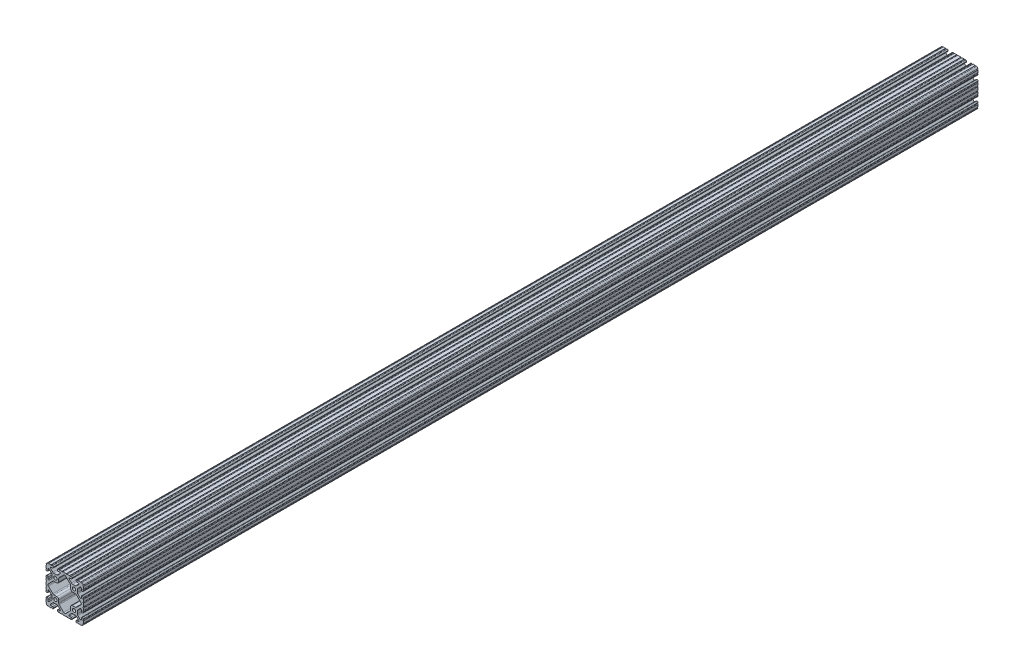
SolidWorks part; units mm, degrees
ref_plane "Front Plane" through (0, 0, 0) normal (0, 0, 1) x (1, 0, 0)
ref_plane "Top Plane" through (0, 0, 0) normal (0, 1, 0) x (1, 0, 0)
ref_plane "Right Plane" through (0, 0, 0) normal (1, 0, 0) x (0, 0, -1)
sketch "Sketch2" plane through (0, 0, 0) normal (0, 0, 1) x (1, 0, 0)
  line L0 (19.05, 38.1) -> (19.05, -38.1) construction
  line L1 (-38.1, 0) -> (38.1, 0) construction
  line L2 (23.114, -38.1) -> (38.1, -38.1)
  line L3 (38.1, -38.1) -> (38.1, -23.114)
  line L4 (23.114, -38.1) -> (23.114, -34.036)
  line L5 (23.114, -34.036) -> (31.1623, -34.036)
  line L6 (31.1623, -34.036) -> (23.1613, -26.035)
  line L7 (19.05, -19.05) -> (38.1, -38.1) construction
  line L8 (38.1, -23.114) -> (34.036, -23.114)
  line L9 (34.036, -23.114) -> (34.036, -31.1623)
  line L10 (34.036, -31.1623) -> (26.035, -23.1613)
  line L11 (0, 38.1) -> (0, -38.1) construction
  line L12 (-13.2459, -13.2459) -> (13.2459, 13.2459) construction
  circle A0 centre (19.05, -19.05) radius 3.3274
  arc A1 (28.0463, -34.036) -> (28.959, -31.8326) centre (28.0463, -32.7453) ccw construction
  point P8 (19.05, -26.035)
  dimension "Center Hole Diameter" = 6.6548
  dimension "Rail Height" = 76.2
  dimension "T-Slot Width" = 8.128
  dimension "Slot Inner Width" = 20.574
  dimension "Thickness" = 4.064
  dimension "Slot Depth" = 8.001
  dimension "D1" = 4.064
  dimension "C to C" = 38.1
  dimension "Rail Width" = 76.2
  dimension "D3" = 38.1
  dimension "D2" = 45
  dimension "Diagonal" = 37.465
sketch "Sketch3" plane through (0, 0, 0) normal (1, 0, 0) x (0, 0, -1)
  line L0 (-914.4, -38.1) -> (914.4, -38.1) construction
  line L1 (-889, 0) -> (889, 0) construction
  dimension "Length" = 1828.8
  dimension "D1" = 25.4
sketch "Sketch4" plane through (0, 0, 0) normal (0, 0, 1) x (1, 0, 0)
  line L0 (24.8412, -38.1) -> (33.3502, -38.1)
  line L1 (23.114, -38.1) -> (38.1, -38.1) construction
  line L2 (23.114, -38.1) -> (23.114, -34.036) construction
  line L3 (23.114, -34.036) -> (31.1623, -34.036) construction
  line L4 (23.114, -35.7632) -> (23.114, -36.3728)
  line L5 (24.8412, -34.036) -> (28.0463, -34.036)
  line L6 (19.05, -26.035) -> (21.883, -26.035)
  line L7 (31.1623, -34.036) -> (23.1613, -26.035) construction
  line L8 (24.0652, -26.9389) -> (28.959, -31.8326)
  line L9 (38.1, -38.1) -> (38.1, -23.114) construction
  line L10 (34.036, -31.1623) -> (26.035, -23.1613) construction
  line L11 (34.036, -23.114) -> (34.036, -31.1623) construction
  line L12 (34.036, -28.0463) -> (34.036, -24.8412)
  line L13 (38.1, -23.114) -> (34.036, -23.114) construction
  line L14 (35.7632, -23.114) -> (36.3728, -23.114)
  line L15 (38.1, -24.8412) -> (38.1, -33.3502)
  line L16 (31.8326, -28.959) -> (26.9389, -24.0652)
  line L17 (26.035, -19.05) -> (26.035, -21.883)
  line L19 (19.05, -26.035) -> (19.05, -22.3774)
  line L20 (19.05, 38.1) -> (19.05, -38.1) construction
  line L21 (26.035, -19.05) -> (22.3774, -19.05)
  arc A0 (23.114, -36.3728) -> (24.8412, -38.1) centre (24.8412, -36.3728) ccw
  circle A1 centre (19.05, -19.05) radius 3.3274 construction
  arc A2 (23.114, -35.7632) -> (24.8412, -34.036) centre (24.8412, -35.7632) cw
  arc A3 (28.0463, -34.036) -> (28.959, -31.8326) centre (28.0463, -32.7453) ccw
  arc A4 (21.883, -26.035) -> (24.0652, -26.9389) centre (21.883, -29.1211) cw
  arc A5 (33.3502, -38.1) -> (38.1, -33.3502) centre (33.3502, -33.3502) ccw
  arc A6 (31.8326, -28.959) -> (34.036, -28.0463) centre (32.7453, -28.0463) ccw
  arc A7 (34.036, -24.8412) -> (35.7632, -23.114) centre (35.7632, -24.8412) cw
  arc A8 (36.3728, -23.114) -> (38.1, -24.8412) centre (36.3728, -24.8412) cw
  arc A9 (26.9389, -24.0652) -> (26.035, -21.883) centre (29.1211, -21.883) cw
  arc A11 (19.05, -22.3774) -> (22.3774, -19.05) centre (19.05, -19.05) ccw
  dimension "D1" = 4.7498
  dimension "D2" = 3.0861
  dimension "D3" = 1.7272
extrude "Boss-Extrude1" add sketch "Sketch4" along normal mid plane 1828.8
sketch "Sketch5" plane through (0, 0, 0) normal (0, 0, 1) x (1, 0, 0)
  line L0 (23.114, -38.1) -> (38.1, -38.1) construction
  line L1 (24.8412, -34.036) -> (28.0463, -34.036) construction
  line L3 (19.05, -19.05) -> (38.1, -38.1) construction
  line L4 (28.0463, -34.036) -> (28.0463, -38.1) construction
  line L5 (24.0652, -26.9389) -> (35.2263, -38.1) construction
  line L6 (24.0652, -26.9389) -> (28.959, -31.8326) construction
  circle A0 centre (33.7895, -38.1) radius 1.016
  circle A1 centre (27.0303, -38.1) radius 1.016
  circle A2 centre (38.1, -33.7895) radius 1.016
  circle A3 centre (38.1, -27.0303) radius 1.016
  point P10 (26.4438, -34.036)
  dimension "D1" = 2.032
extrude "Cut-Extrude1" cut sketch "Sketch5" against normal through all both and the other way through all
mirror "Mirror1" about plane through (26.035, -19.05, 914.4) normal (0, -1, 0) of bodies 137 134
mirror "Mirror4" about plane through (19.05, -12.065, 914.4) normal (1, 0, 0) of bodies 135 139
sketch "Sketch6" plane through (0, 0, 0) normal (0, 0, 1) x (1, 0, 0)
  line L0 (38.1, -3.2945) -> (38.1, 0)
  line L2 (-38.1, 0) -> (38.1, 0) construction
  line L3 (32.7735, 0) -> (32.7735, -4.3105)
  line L4 (32.7735, -4.3105) -> (37.084, -4.3105)
  line L5 (19.05, -19.05) -> (38.1, -38.1) construction
  line L10 (32.7735, 0) -> (38.1, 0)
  line L11 (0, -32.7735) -> (4.3105, -32.7735)
  line L12 (0, -32.7735) -> (0, -38.1)
  line L13 (3.2945, -38.1) -> (0, -38.1)
  line L14 (4.3105, -32.7735) -> (4.3105, -37.084)
  circle A0 centre (38.1, -4.3105) radius 1.016 construction
  arc A1 (38.1, -3.2945) -> (37.084, -4.3105) centre (38.1, -4.3105) ccw
  arc A3 (32.7735, 0) -> (34.7812, -0.2207) centre (33.7895, 0) ccw construction
  arc A4 (37.8793, -3.3188) -> (38.1, -5.3265) centre (38.1, -4.3105) ccw construction
  arc A7 (3.2945, -38.1) -> (4.3105, -37.084) centre (4.3105, -38.1) cw
extrude "Boss-Extrude2" add sketch "Sketch6" along normal mid plane 1828.8
sketch "Sketch7" plane through (0, 0, 0) normal (0, 0, 1) x (1, 0, 0)
  line L0 (26.5121, -8.7142) -> (33.1943, -2.032)
  line L1 (24.0652, -11.1611) -> (28.959, -6.2674) construction
  line L3 (19.05, 0) -> (34.036, 0)
  line L5 (19.05, 0) -> (26.5121, -8.7142)
  line L7 (19.05, 38.1) -> (19.05, -38.1) construction
  line L8 (-13.2459, 13.2459) -> (13.2459, -13.2459) construction
  line L9 (19.05, -19.05) -> (38.1, -38.1) construction
  line L10 (-13.2459, -13.2459) -> (13.2459, 13.2459) construction
  line L11 (12.065, -21.883) -> (12.065, -16.217) construction
  line L12 (16.217, -12.065) -> (21.883, -12.065) construction
  line L13 (12.065, -16.0968) -> (12.065, -21.883)
  line L14 (34.036, -13.2588) -> (34.036, -10.0537) construction
  line L15 (11.1611, -24.0652) -> (2.032, -33.1943)
  line L16 (6.2674, -28.959) -> (11.1611, -24.0652) construction
  line L17 (0, 38.1) -> (0, -38.1) construction
  line L18 (10.0537, -34.036) -> (13.2588, -34.036) construction
  line L19 (0, -34.036) -> (0, 0)
  line L20 (0, 0) -> (16.0968, 0)
  line L21 (-38.1, 0) -> (38.1, 0) construction
  line L22 (16.0968, 0) -> (16.0968, -12.065)
  arc A0 (33.1943, -2.032) -> (34.036, 0) centre (31.1623, 0) ccw
  arc A1 (12.065, -16.0968) -> (16.0968, -12.065) centre (16.0968, -16.0968) cw
  arc A2 (12.065, -21.883) -> (11.1611, -24.0652) centre (8.9789, -21.883) cw
  arc A4 (2.032, -33.1943) -> (0, -34.036) centre (0, -31.1623) cw
extrude "Cut-Extrude2" cut sketch "Sketch7" against normal through all both and the other way through all
mirror "Mirror2" about plane through (0, 0, 0) normal (0, 1, 0) of bodies 139 135
mirror "Mirror3" about plane through (0, 0, 0) normal (1, 0, 0) of bodies 136
equation "\"D1@Boss-Extrude1\"=\"Length@Sketch3\""
equation "\"D1@Sketch2\"=\"Thickness@Sketch2\""
equation "\"D2@Sketch4\"=\"Slot Inner Width@Sketch2\"*0.15"
equation "\"D1@Sketch4\"=\"D3@Sketch4\"*2.75"
equation "\"D3@Sketch4\"=\"Thickness@Sketch2\"*0.425"
equation "\"D1@Sketch5\"=\"Thickness@Sketch2\"*0.5"
equation "\"D1@Boss-Extrude2\"=\"Length@Sketch3\""
equation "\"D3@Sketch2\"=\"C to C@Sketch2\""
